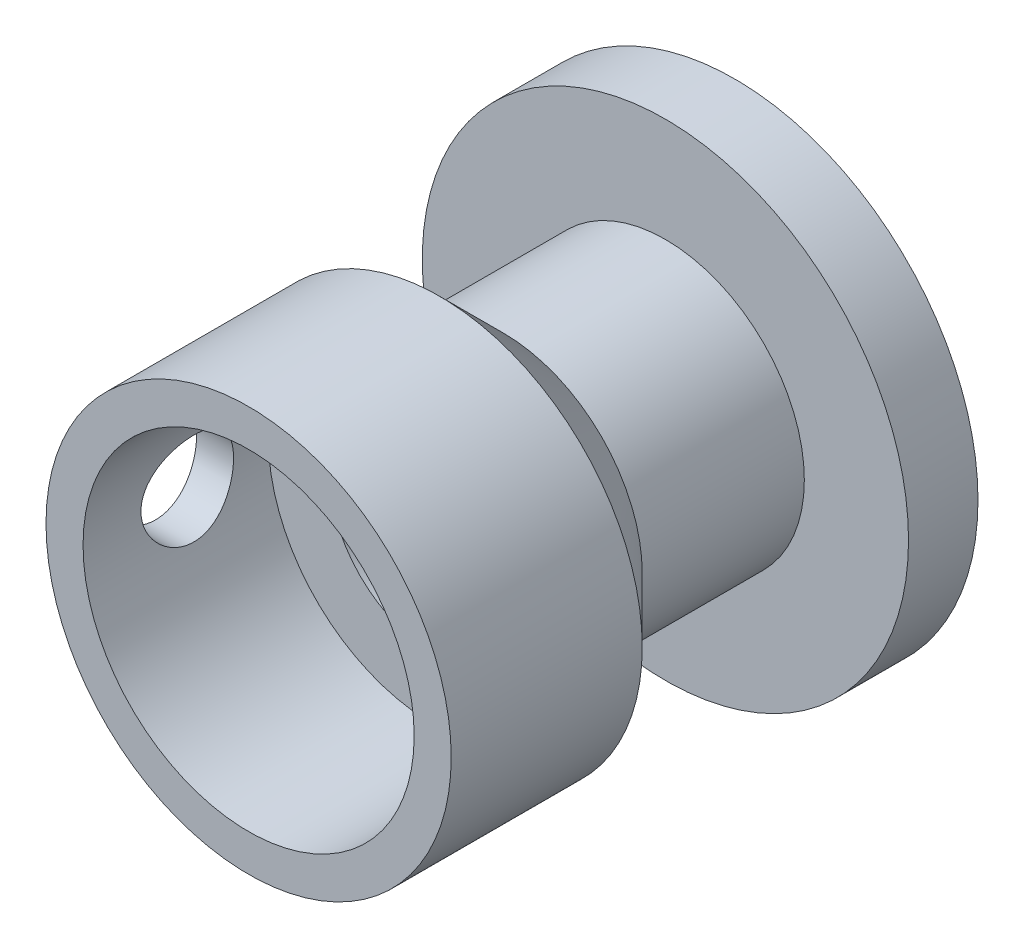
SolidWorks part; units mm, degrees
ref_plane "Ön Düzlem" through (0, 0, 0) normal (0, 0, 1) x (1, 0, 0)
ref_plane "Üst Düzlem" through (0, 0, 0) normal (0, 1, 0) x (1, 0, 0)
ref_plane "Sağ Düzlem" through (0, 0, 0) normal (1, 0, 0) x (0, 0, -1)
sketch "Sketch1" plane through (0, 0, 0) normal (0, 0, 1) x (1, 0, 0)
  circle A0 centre (0, 0) radius 10.5
  dimension "D1" = 21
extrude "Boss-Extrude2" add sketch "Sketch1" along normal blind 3
sketch "Sketch2" plane through (0, 0, 3) normal (0, 0, 1) x (1, 0, 0)
  circle A0 centre (0, 0) radius 6
  dimension "D1" = 12
extrude "Boss-Extrude3" add sketch "Sketch2" along normal blind 10
sketch "Sketch3" plane through (0, 0, 13) normal (0, 0, 1) x (1, 0, 0)
  circle A0 centre (0, 0) radius 4.5
  dimension "D1" = 9
extrude "Cut-Extrude1" cut sketch "Sketch3" against normal blind 4
sketch "Sketch4" plane through (0, 0, 13) normal (0, 0, 1) x (1, 0, 0)
  circle A1 centre (0, 0) radius 8.75
  dimension "D2" = 17.5
extrude "Boss-Extrude4" add sketch "Sketch4" along normal blind 8
sketch "Sketch5" plane through (0, 0, 21) normal (0, 0, 1) x (1, 0, 0)
  circle A0 centre (0, 0) radius 7.15
  dimension "D1" = 14.3
chamfer "Chamfer1" distance 3 angle 45 1 edges at (6, 0, 13)
extrude "Cut-Extrude3" cut sketch "Sketch5" against normal blind 8
sketch "Sketch6" plane through (0, 0, 9) normal (0, 0, 1) x (1, 0, 0)
  circle A0 centre (0, 0) radius 1.5
  dimension "D1" = 3
extrude "Cut-Extrude4" cut sketch "Sketch6" against normal up to surface (9 mm away) up to face at (10.5, 0, 0)
sketch "Sketch7" plane through (0, 0, 0) normal (1, 0, 0) x (0, 0, -1)
  line L0 (-12.75, 8.75) -> (-12.75, -8.75) construction
  line L1 (-12.75, 8.75) -> (-21, 8.75) construction
  circle A0 centre (-16.5, 0) radius 2
  dimension "D2" = 4
  dimension "D1" = 3.75
  dimension "D3" = 8.75
extrude "Cut-Extrude5" cut sketch "Sketch7" against normal up to surface (8.75 mm away) up to face at (8.75, 0, 12.75)
